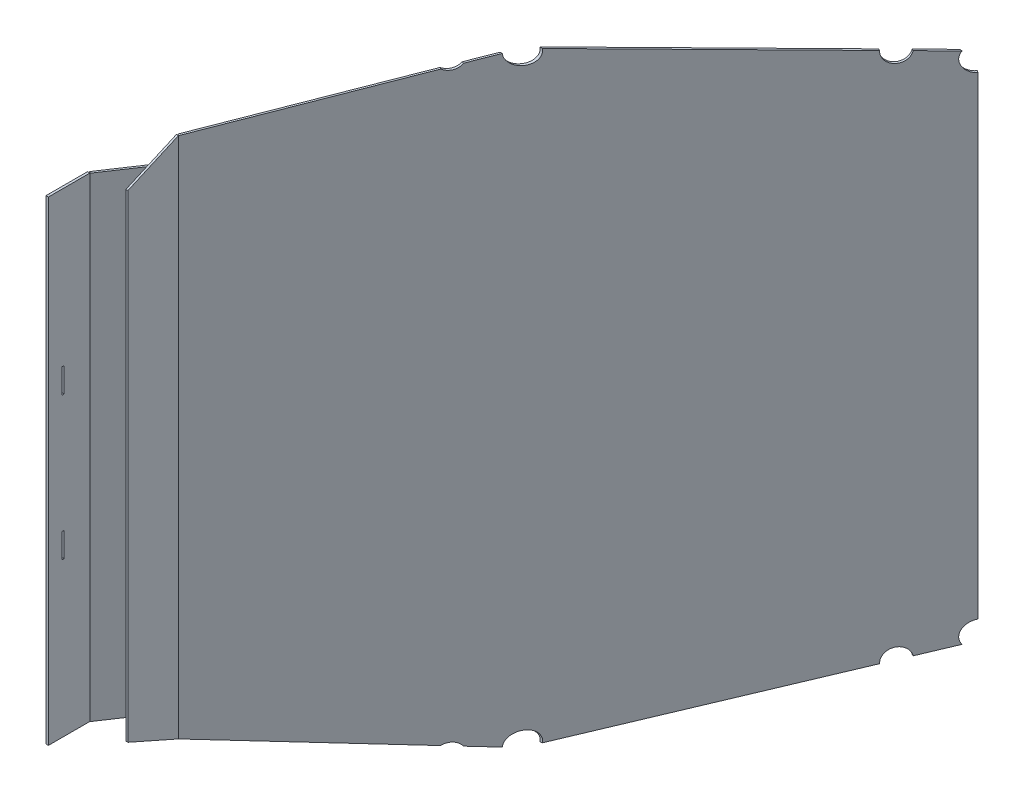
SolidWorks part; units mm, degrees
material "6061-T6 (SS)"
ref_plane "X-Y Datum" through (0, 0, 0) normal (0, 0, 1) x (1, 0, 0)
ref_plane "X-Z Datum" through (0, 0, 0) normal (0, 1, 0) x (1, 0, 0)
ref_plane "Y-Z Datum" through (0, 0, 0) normal (1, 0, 0) x (0, 0, -1)
ref_plane "Plane2" through (251.4767, 0, 168.3074) normal (-0.831, 0, -0.5562) x (-0.5562, 0, 0.831)
sketch "Sketch3" plane through (251.4767, 0, 168.3074) normal (-0.831, 0, -0.5562) x (-0.5562, 0, 0.831)
  line L0 (-187.2045, -273.05) -> (-187.2045, 273.05)
  line L1 (-187.2045, 273.05) -> (164.4025, 323.85)
  line L2 (429.2995, -279.4) -> (429.2995, -254)
  line L3 (429.2995, 279.4) -> (164.4025, 323.85)
  line L4 (-187.2045, 0) -> (429.2995, 0)
  line L5 (429.2995, -279.4) -> (164.4025, -323.85)
  line L6 (-187.2045, -273.05) -> (164.4025, -323.85)
  line L7 (429.2995, -254) -> (497.2625, -254)
  line L9 (55, 0) -> (-55, 0) construction
  line L10 (429.2995, 254) -> (497.2625, 254)
  line L11 (497.2625, 254) -> (497.2625, -254)
  line L12 (429.2995, 254) -> (429.2995, 279.4)
  dimension "D1" = 273.05
  dimension "D2" = 279.4
  dimension "D3" = 323.85
  dimension "D4" = 25.4
extrude "Boss-Extrude1" add sketch "Sketch3" along normal blind 2.159 contours L0 L4 L2 L3 L1 | L0 L6 L5 L2 L4 region at (350.3587, -136.525, 20.5628)
ref_plane "Plane3" through (12.7, 0, 0) normal (-1, 0, 0) x (0, 0, 1)
sketch "Sketch4" plane through (12.7, 0, 0) normal (-1, 0, 0) x (0, 0, 1)
  line L2 (525.0759, -279.4) -> (525.0759, 279.4)
  line L3 (525.0759, 279.4) -> (579.0509, 255.5299)
  line L5 (579.0509, 255.5299) -> (579.0509, -255.5299)
  line L6 (525.0759, -279.4) -> (579.0509, -255.5299)
  dimension "D1" = 53.975
extrude "Boss-Extrude2" add sketch "Sketch4" along normal blind 2.159 separate body contours L6 L5 | L5 region at (12.7, 0, 551.662)
ref_plane "Plane4" through (825.5, 177.8, 47.625) normal (-0.9802, 0.1844, -0.0728) x (-0.0715, 0.0135, 0.9973)
sketch "Sketch5" plane through (825.5, 177.8, 47.625) normal (-0.9802, 0.1844, -0.0728) x (-0.0715, 0.0135, 0.9973)
  circle A0 centre (0, 0) radius 12.954
  dimension "D1" = 25.908
extrude "Cut-Extrude1" cut sketch "Sketch5" along normal blind 621.665
ref_plane "Plane5" through (825.5, 227.0125, 304.8) normal (-0.8987, 0.1001, -0.4271) x (-0.4245, 0.0473, 0.9042)
sketch "Sketch6" plane through (825.5, 227.0125, 304.8) normal (-0.8987, 0.1001, -0.4271) x (-0.4245, 0.0473, 0.9042)
  circle A0 centre (0, 0) radius 12.954
  dimension "D1" = 25.908
extrude "Cut-Extrude2" cut sketch "Sketch6" along normal through all
ref_plane "Plane6" through (825.5, 227.0125, 304.8) normal (-0.9902, 0.1398, -0.0002) x (-0.0002, 0, 1)
sketch "Sketch7" plane through (825.5, 227.0125, 304.8) normal (-0.9902, 0.1398, -0.0002) x (-0.0002, 0, 1)
  circle A0 centre (0, 0) radius 12.954
  dimension "D1" = 25.908
extrude "Cut-Extrude3" cut sketch "Sketch7" along normal through all
ref_plane "Plane7" through (825.5, 220.2924, 603.4647) normal (-0.9311, 0.1391, -0.3371) x (-0.3334, 0.0498, 0.9415)
sketch "Sketch8" plane through (825.5, 220.2924, 603.4647) normal (-0.9311, 0.1391, -0.3371) x (-0.3334, 0.0498, 0.9415)
  circle A0 centre (0, 0) radius 12.954
  dimension "D1" = 25.908
extrude "Cut-Extrude4" cut sketch "Sketch8" along normal through all
mirror "Mirror1" about plane through (0, 0, 0) normal (0, 1, 0) of "Cut-Extrude4", "Cut-Extrude3", "Cut-Extrude2", "Cut-Extrude1"
ref_plane "Plane9" through (-25.4, 0, 0) normal (1, 0, 0) x (0, 0, -1)
sketch "Sketch10" plane through (-25.4, 0, 0) normal (1, 0, 0) x (0, 0, -1)
  line L0 (-581.5564, 254) -> (-581.5564, -254) construction
  line L1 (-581.5564, 254) -> (-581.5564, -254)
  line L2 (-581.5564, 254) -> (-626.0064, 254)
  line L3 (-581.5564, -254) -> (-626.0064, -254)
  line L4 (-626.0064, 254) -> (-626.0064, -254)
  line L13 (-609.1326, 63.1148) -> (-609.1326, 89.3994)
  line L14 (-609.1326, 89.3994) -> (-611.6788, 89.3994)
  line L15 (-611.6788, 89.3994) -> (-611.6788, 63.1148)
  line L16 (-611.6788, 63.1148) -> (-609.1326, 63.1148)
  line L21 (210.3724, 0) -> (-210.3724, 0) construction
  line L22 (-611.6788, -63.1148) -> (-609.1326, -63.1148)
  line L23 (-609.1326, -89.3994) -> (-611.6788, -89.3994)
  line L24 (-609.1326, -63.1148) -> (-609.1326, -89.3994)
  line L25 (-611.6788, -89.3994) -> (-611.6788, -63.1148)
  dimension "D1" = 44.45
extrude "Boss-Extrude3" add sketch "Sketch10" against normal blind 2.54 separate body
